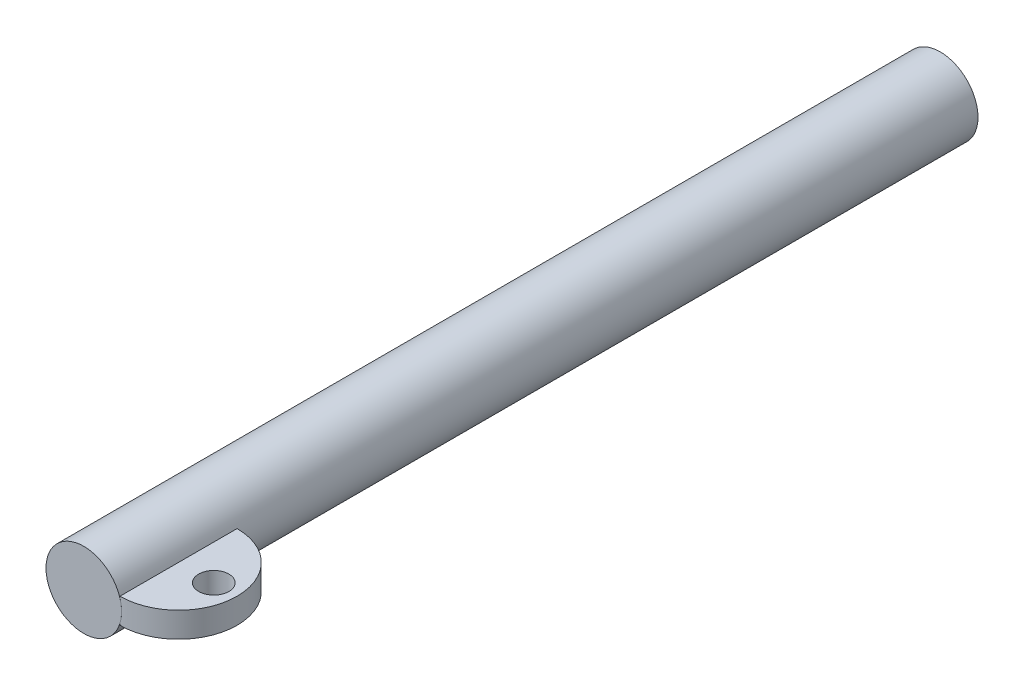
SolidWorks part; units mm, degrees
ref_plane "Front" through (0, 0, 0) normal (0, 0, 1) x (1, 0, 0)
ref_plane "Top" through (0, 0, 0) normal (0, 1, 0) x (1, 0, 0)
ref_plane "Right" through (0, 0, 0) normal (1, 0, 0) x (0, 0, -1)
sketch "Sketch1" plane through (0, 0, 0) normal (0, 0, 1) x (1, 0, 0)
  circle A0 centre (0, 0) radius 19.05
  point P3 (-19.05, 0)
  dimension "D1" = 38.1
extrude "Base-Extrude" add sketch "Sketch1" against normal blind 431.8
ref_plane "Plane2" through (0, 0, 0) normal (0, 1, 0) x (-1, 0, 0)
sketch "Sketch4" plane through (0, 0, 0) normal (0, 1, 0) x (-1, 0, 0)
  line L0 (-18.2312, -59.0746) -> (-18.2312, 0)
  arc A0 (-18.2312, 0) -> (-18.2312, -59.0746) centre (-18.2312, -29.5373) ccw
  circle A1 centre (-36.0112, -29.5373) radius 7.62
  dimension "D1" = 17.78
extrude "Boss-Extrude1" add sketch "Sketch4" along normal blind 6.35 and the other way blind 6.35
